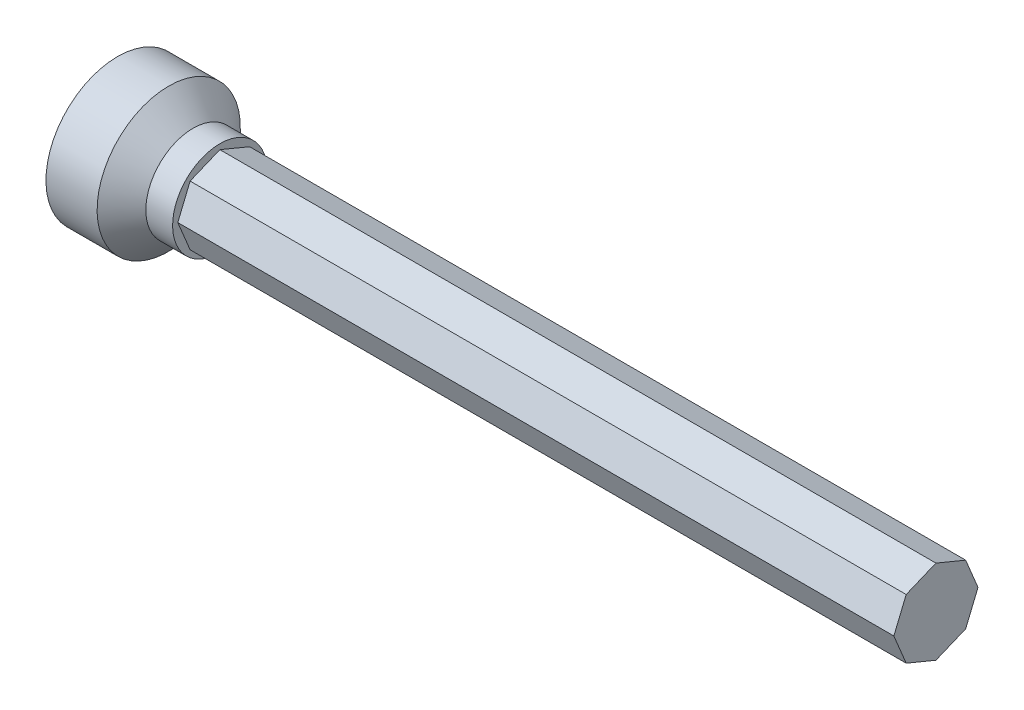
SolidWorks part; units mm, degrees
ref_plane "Front Plane" through (0, 0, 0) normal (0, 0, 1) x (1, 0, 0)
ref_plane "Top Plane" through (0, 0, 0) normal (0, 1, 0) x (1, 0, 0)
ref_plane "Right Plane" through (0, 0, 0) normal (1, 0, 0) x (0, 0, -1)
sketch "Sketch1" plane through (0, 0, 0) normal (1, 0, 0) x (0, 0, -1)
  line L7 (-2.0565, 0) -> (-1.4542, -1.4542)
  line L8 (-1.4542, -1.4542) -> (0, -2.0565)
  line L9 (0, -2.0565) -> (1.4542, -1.4542)
  line L10 (1.4542, -1.4542) -> (2.0565, 0)
  line L11 (2.0565, 0) -> (1.4542, 1.4542)
  line L12 (1.4542, 1.4542) -> (0, 2.0565)
  line L13 (0, 2.0565) -> (-1.4542, 1.4542)
  line L14 (-1.4542, 1.4542) -> (-2.0565, 0)
  circle A1 centre (0, 0) radius 1.9 construction
extrude "Boss-Extrude1" add sketch "Sketch1" along normal blind 35
sketch "Sketch4" plane through (0, 0, 0) normal (0, 0, 1) x (1, 0, 0)
  line L0 (0, 0) -> (-5, 0)
  line L1 (-5, 0) -> (-5, 3.5)
  line L6 (-1.3094, 2.3094) -> (0, 2.3094)
  line L7 (0, 2.3094) -> (0, 0)
  line L8 (-5, 3.5) -> (-2.5, 3.5)
  line L9 (-1.3094, 2.3094) -> (-2.5, 3.5)
  point P3 (0, 0)
  dimension "D1" = 3.5
revolve "Revolve1" add sketch "Sketch4" angle 360 about L0
